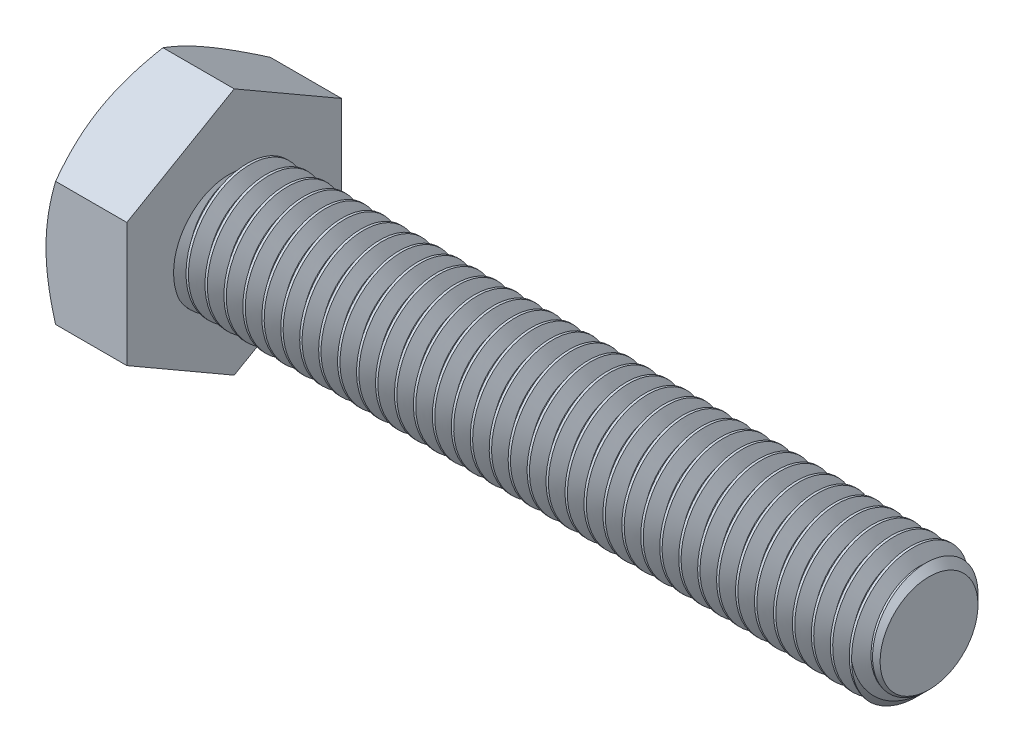
SolidWorks part; units mm, degrees
ref_plane "Front Plane" through (0, 0, 0) normal (0, 0, 1) x (1, 0, 0)
ref_plane "Top Plane" through (0, 0, 0) normal (0, 1, 0) x (1, 0, 0)
ref_plane "Right Plane" through (0, 0, 0) normal (1, 0, 0) x (0, 0, -1)
sketch "Sketch1" plane through (0, 0, 0) normal (0, 0, 1) x (1, 0, 0)
  line L0 (-30.7, 0) -> (30.7, 0) construction
  line L1 (-24.3, 8.5) -> (-24.3, -8.5) construction
  line L2 (-30.7, 8.5) -> (-30.7, -8.5) construction
  line L3 (30.7, 5) -> (30.7, -5) construction
  point P8 (25.45, -5)
  dimension "Thread Dia" = 10
  dimension "Hex" = 17
  dimension "Head Ht" = 6.4
  dimension "Length" = 55
  dimension "D1" = 5.25
ref_plane "Plane2" through (30.7, 0, 0) normal (1, 0, 0) x (0, 0, -1)
sketch "Sketch2" plane through (30.7, 0, 0) normal (1, 0, 0) x (0, 0, -1)
  circle A0 centre (0, 0) radius 5
extrude "Boss-Extrude1" add sketch "Sketch2" against normal up to vertex (55 mm away) up to point (-24.3, -8.5, 0)
sketch "Sketch4" plane through (30.7, 0, 0) normal (1, 0, 0) x (0, 0, -1)
  circle A1 centre (0, 0) radius 5
  circle A2 centre (0, 0) radius 5
  dimension "D1" = 0
curve "Helix/Spiral1" pitch 1.5 height 56.5 turns 37.6667 parameters "Pitch"=1.5
chamfer "Chamfer1" distance 1.125 angle 45 1 edges at (30.7, 0, -5)
sketch "Sketch5" plane through (0, 0, 0) normal (0, 0, 1) x (1, 0, 0)
  line L0 (30.7, 5) -> (31.2625, 4.0257)
  line L1 (31.2625, 4.0257) -> (31.45, 4.0257)
  line L2 (31.45, 4.0257) -> (32.0125, 5)
  line L3 (30.7, 5) -> (32.0125, 5)
  line L4 (31.3563, 4.0257) -> (31.3563, 5) construction
  line L5 (30.9813, 4.5129) -> (31.7313, 4.5129) construction
  line L6 (30.7, -5) -> (30.7, 5) construction
  dimension "D1" = 60
  dimension "D2" = 0.1875
  dimension "D3" = 0.75
sweep "Cut-Sweep1" cut profiles "Sketch5" path "Helix/Spiral1"
sketch "Sketch3" plane through (-24.3, 0, 0) normal (-1, 0, 0) x (0, 0, 1)
  line L0 (0, 8.5) -> (0, -8.5) construction
  line L1 (-8.5, -4.9075) -> (0, -9.815)
  line L2 (0, -9.815) -> (8.5, -4.9075)
  line L3 (8.5, -4.9075) -> (8.5, 4.9075)
  line L4 (8.5, 4.9075) -> (0, 9.815)
  line L5 (0, 9.815) -> (-8.5, 4.9075)
  line L6 (-8.5, 4.9075) -> (-8.5, -4.9075)
  circle A0 centre (0, 0) radius 8.5 construction
extrude "Boss-Extrude2" add sketch "Sketch3" along normal up to vertex (6.4 mm away) up to point (-30.7, -8.5, 0)
sketch "Sketch6" plane through (-30.7, 0, 0) normal (-1, 0, 0) x (0, 0, 1)
  circle A0 centre (0, 0) radius 8.5 construction
  circle A1 centre (0, 0) radius 8.5
extrude "Cut-Extrude1" cut sketch "Sketch6" against normal through all draft 60 flip side to cut
sketch "Sketch9" plane through (0, 0, 0) normal (0, 0, 1) x (1, 0, 0)
  line L0 (-24.3, 5) -> (-24.3, 0)
  line L1 (-24.3, 0) -> (-18.3, 0)
  line L2 (-18.3, 0) -> (-23.3, 5)
  line L3 (-23.3, 5) -> (-24.3, 5)
  line L4 (-30.7, 0) -> (30.7, 0) construction
  line L5 (-24.3, 8.5) -> (-24.3, -8.5) construction
  line L6 (30.7, 5) -> (30.7, -5) construction
  dimension "D1" = 45
  dimension "MinThreadLg" = 54
revolve "Revolve1" [suppressed] add sketch "Sketch9" angle 360 about L1
equation "\"D2@Sketch5\" = \"Pitch@Helix/Spiral1\"*.125"
equation "\"D3@Sketch5\" = \"Pitch@Helix/Spiral1\"*.50"
equation "\"D3@Helix/Spiral1\" = \"Length@Sketch1\"+\"Pitch@Helix/Spiral1\""
equation "\"D1@Chamfer1\" = \"Pitch@Helix/Spiral1\"*.750"
equation "\"D1@Sketch1\" = \"Pitch@Helix/Spiral1\"*3.50"
